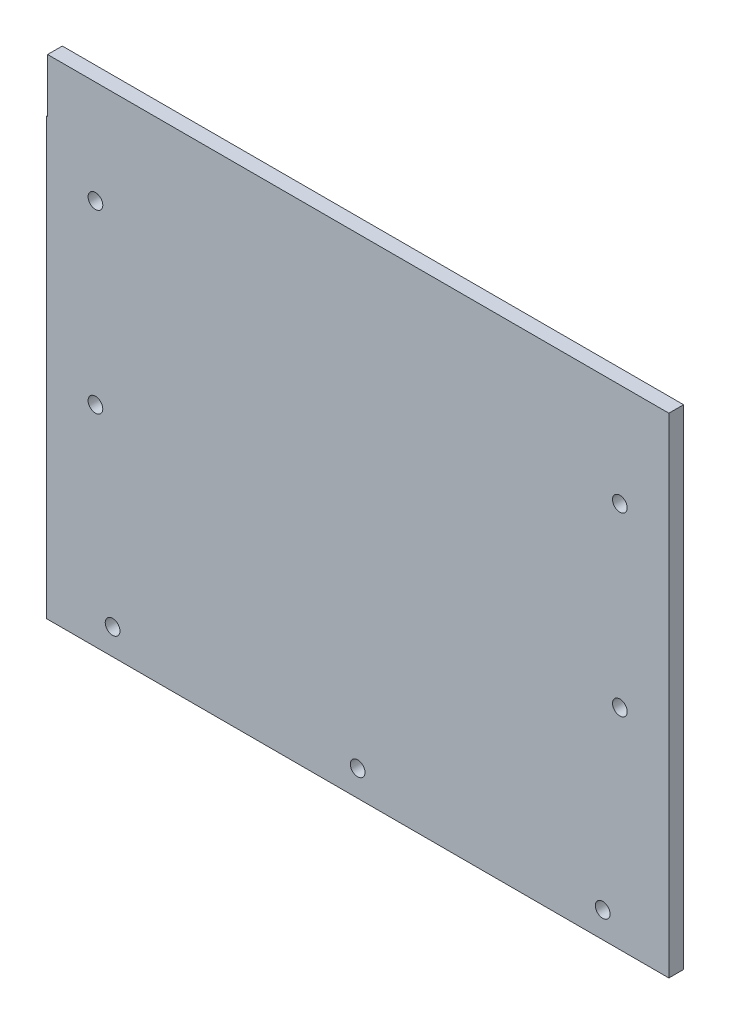
SolidWorks part; units mm, degrees
ref_plane "前视基准面" through (0, 0, 0) normal (0, 0, 1) x (1, 0, 0)
ref_plane "上视基准面" through (0, 0, 0) normal (0, 1, 0) x (1, 0, 0)
ref_plane "右视基准面" through (0, 0, 0) normal (1, 0, 0) x (0, 0, -1)
sketch "草图1" plane through (0, 0, 0) normal (0, 0, 1) x (1, 0, 0)
  line L1 (63.5, -46) -> (-63.5, -46)
  line L2 (63.5, -46) -> (63.5, 46)
  line L3 (63.5, 46) -> (-63.5, 46)
  line L4 (-63.5, -46) -> (-63.5, 46)
  line L5 (63.5, -46) -> (-63.5, 46) construction
  line L6 (63.5, 46) -> (-63.5, -46) construction
  point P0 (0, 0)
  dimension "D1" = 127
  dimension "D2" = 92
extrude "凸台-拉伸1" add sketch "草图1" along normal blind 3
sketch "草图2" plane through (0, 0, 3) normal (0, 0, 1) x (1, 0, 0)
  line L0 (-63.5, -46) -> (63.5, -46) construction
  line L1 (0, -46) -> (0, -37.5) construction
  line L2 (0, -37.5) -> (50, -37.5)
  line L3 (0, -37.5) -> (-50, -37.5)
  line L4 (-50, -37.5) -> (-16.0719, -37.5)
  circle A0 centre (0, -37.5) radius 1.5
  circle A1 centre (50, -37.5) radius 1.5
  circle A2 centre (-50, -37.5) radius 1.5
  dimension "D2" = 3
  dimension "D4" = 3
  dimension "D5" = 3
  dimension "D1" = 8.5
  dimension "D3" = 50
  dimension "D6" = 50
extrude "切除-拉伸1" cut sketch "草图2" against normal through all contours A2 | L2 A0 L3 | L1 A0 L2 | A0 L1 L3 | A1 region at (-0.6366, -38.1366, 3) region at (-51.4576, -37.5, 3) region at (50, -36.0424, 3) region at (0.6366, -38.1366, 3) region at (0, -36.8634, 3)
sketch "草图3" plane through (0, 0, 3) normal (0, 0, 1) x (1, 0, 0)
  line L0 (0, 46) -> (0, 30.213) construction
  line L1 (-63.5, 46) -> (-53.5, 46)
  line L2 (-63.5, 46) -> (-63.5, 36)
  line L3 (-63.5, 36) -> (-53.5, 36)
  line L4 (-53.5, 46) -> (-53.5, 36)
  line L5 (63.5, 46) -> (-63.5, 46) construction
  line L6 (53.5, 46) -> (53.5, 36)
  line L7 (63.5, 36) -> (53.5, 36)
  line L8 (63.5, 46) -> (63.5, 36)
  line L9 (63.5, 46) -> (53.5, 46)
  line L10 (-63.5, 0) -> (-53.5, 0)
  line L11 (-63.5, 46) -> (-63.5, -46) construction
  circle A0 centre (-53.5, 36) radius 1.5
  circle A1 centre (53.5, 36) radius 1.5
  circle A2 centre (-53.5, 0) radius 1.5
  circle A3 centre (53.5, 0) radius 1.5
  dimension "D3" = 3
  dimension "D4" = 3
  dimension "D1" = 10
  dimension "D2" = 10
  dimension "D5" = 10
extrude "切除-拉伸2" cut sketch "草图3" against normal through all contours L3 A0 L4 | L4 A0 L3 | A1 L7 L6 | A1 L6 L7 | A2 | A3 region at (-53.2878, 35.7878, 3) region at (-54.1366, 36.6366, 3) region at (54.1366, 36.6366, 3) region at (53.2878, 35.7878, 3) region at (-53.5, -1.4576, 3) region at (53.5, 0, 3)
sketch "草图4" plane through (0, 0, 0) normal (0, 0, -1) x (-1, 0, 0)
  line L0 (63.5, 46) -> (63.5, -46) construction
  line L1 (-63.5, -46) -> (63.5, -46)
  line L2 (-63.5, -46) -> (-63.5, -42.8)
  line L3 (-63.5, -42.8) -> (63.5, -42.8)
  line L4 (63.5, -46) -> (63.5, -42.8)
  dimension "D1" = 3.2
extrude "切除-拉伸3" cut sketch "草图4" against normal blind 10
sketch "草图5" plane through (0, 0, 0) normal (0, 0, -1) x (-1, 0, 0)
  line L1 (-63.5, 46) -> (63.2589, 46)
  line L2 (-63.5, 46) -> (-63.5, 57)
  line L3 (-63.5, 57) -> (63.2589, 57)
  line L4 (63.2589, 46) -> (63.2589, 57)
  dimension "D1" = 11
extrude "凸台-拉伸2" add sketch "草图5" against normal blind 3
